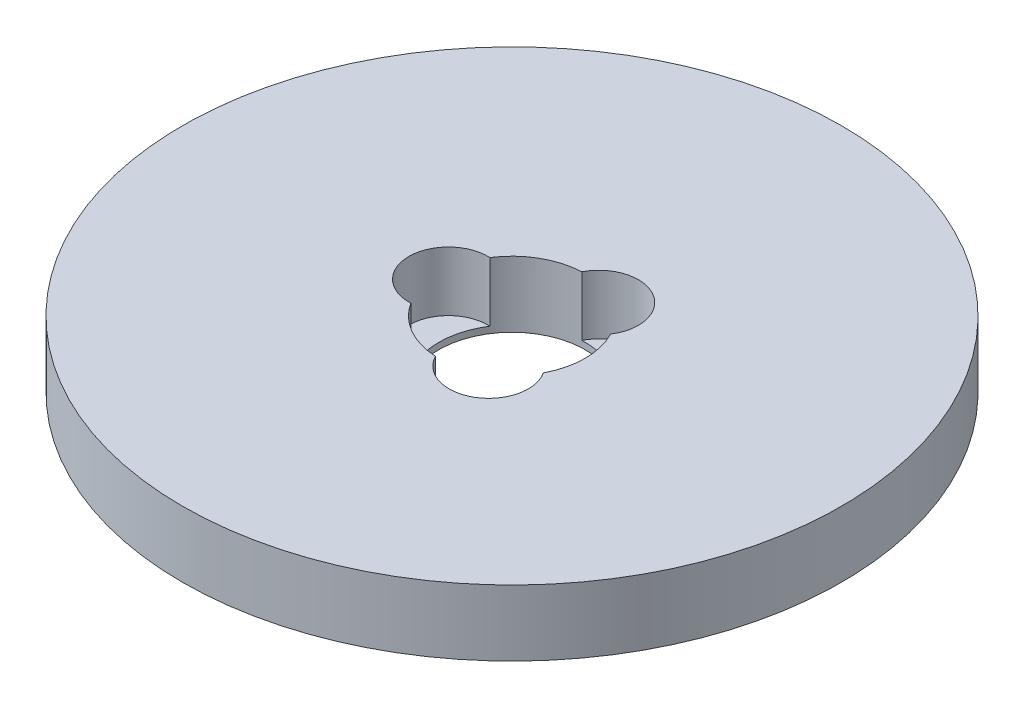
SolidWorks part; units mm, degrees
ref_plane "Front Plane" through (0, 0, 0) normal (0, 0, 1) x (1, 0, 0)
ref_plane "Top Plane" through (0, 0, 0) normal (0, 1, 0) x (1, 0, 0)
ref_plane "Right Plane" through (0, 0, 0) normal (1, 0, 0) x (0, 0, -1)
sketch "Sketch1" plane through (0, 0, 0) normal (0, 1, 0) x (1, 0, 0)
  circle A0 centre (0, 0) radius 45
  dimension "FLANGE_OD" = 90
extrude "Boss-Extrude1" add sketch "Sketch1" along normal blind 9
sketch "Sketch2" plane through (0, 0, 0) normal (0, 1, 0) x (1, 0, 0)
  circle A0 centre (0, 0) radius 10
  dimension "BORE_D" = 20
extrude "Cut-Extrude1" cut sketch "Sketch2" along normal through all
sketch "Sketch3" plane through (0, 9, 0) normal (0, 1, 0) x (1, 0, 0)
  circle A0 centre (0, 0) radius 8.6804 construction
  circle A1 centre (-8.6804, 0) radius 5.4
  dimension "BOLT_D" = 10.7999
  dimension "BOLT_PCD" = 17.3608
extrude "Cut-Extrude2" cut sketch "Sketch3" against normal blind 8.1164
pattern_circular "CirPattern1" count 3 over 360 about axis through (0, 0, 0) along (0, 1, 0) of "Cut-Extrude2"
